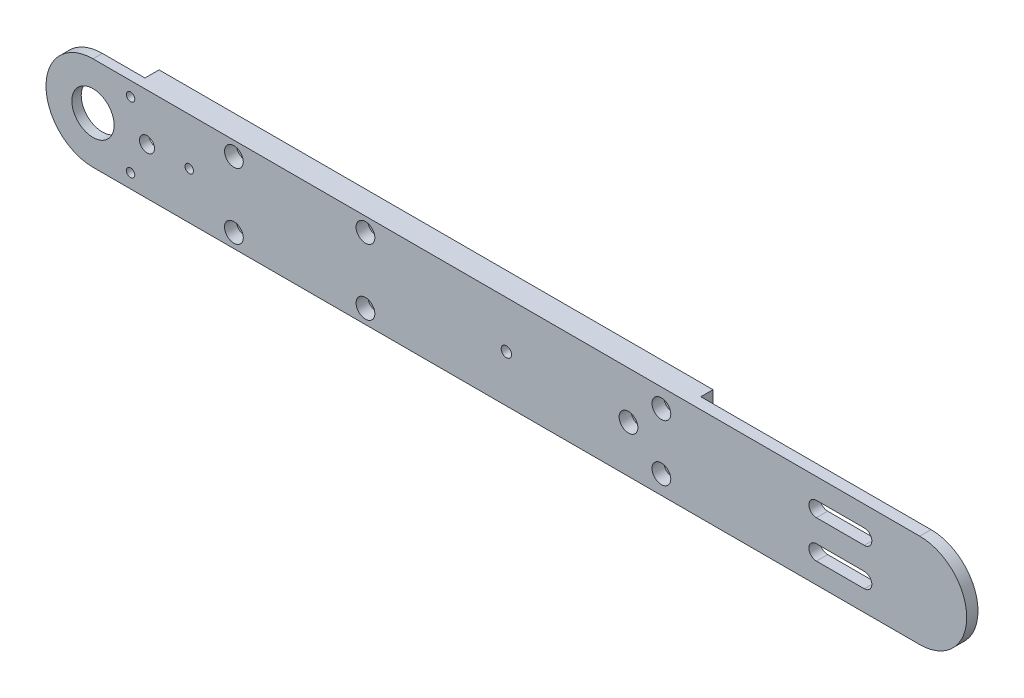
SolidWorks part; units mm, degrees
ref_plane "前视基准面" through (0, 0, 0) normal (0, 0, 1) x (1, 0, 0)
ref_plane "上视基准面" through (0, 0, 0) normal (0, 1, 0) x (1, 0, 0)
ref_plane "右视基准面" through (0, 0, 0) normal (1, 0, 0) x (0, 0, -1)
other "Configuration Table"
sketch "草图1" plane through (0, 0, 0) normal (0, 0, 1) x (1, 0, 0)
  line L0 (0, 0) -> (176, 0) construction
  line L5 (0, 10) -> (176, 10)
  line L6 (0, 10) -> (0, -10)
  line L7 (0, -10) -> (176, -10)
  line L8 (176, 10) -> (176, -10)
  circle A2 centre (0, 0) radius 10
  circle A5 centre (88, 0) radius 2.55
  circle A8 centre (88, 0) radius 1.1
  circle A9 centre (0, 0) radius 2.55
  circle A10 centre (0, 0) radius 1.1
  circle A11 centre (176, 0) radius 10
  dimension "D1" = 20
  dimension "D2" = 176
  dimension "D4" = 2.2
  dimension "D5" = 5.1
  dimension "D3" = 176
extrude "凸台-拉伸1" add sketch "草图1" along normal blind 5 contours A2 | L7 L8 L5 L6 | A11
extrude "切除-拉伸2" cut sketch "草图1<3>" along normal through all contours A10 | A8
sketch "草图1<3>" plane through (0, 0, 0) normal (0, 0, 1) x (1, 0, 0) same geometry as "草图1"
extrude "切除-拉伸3" cut sketch "草图1<4>" along normal blind 2.6 contours A5 | A9
sketch "草图1<4>" plane through (0, 0, 0) normal (0, 0, 1) x (1, 0, 0) same geometry as "草图1"
sketch "草图2" plane through (0, 0, 0) normal (0, 0, -1) x (-1, 0, 0)
  line L0 (0, -10) -> (-176, -10) construction
  line L1 (0, 10) -> (-176, 10) construction
  line L2 (-121, 6) -> (-121, -6) construction
  circle A0 centre (-121, -6) radius 1.25
  circle A1 centre (-121, 6) radius 1.25
  circle A2 centre (-121, -6) radius 2
  circle A3 centre (-121, 6) radius 2
  circle A4 centre (-88, 0) radius 1.1 construction
  circle A5 centre (-114, 0) radius 2
  circle A6 centre (-114, 0) radius 1.25
  circle A7 centre (-58, 7) radius 1.25
  circle A9 centre (-58, 7) radius 2
  circle A10 centre (-30, 7) radius 2
  circle A11 centre (-30, 7) radius 1.25
  circle A12 centre (-58, -7) radius 2
  circle A13 centre (-58, -7) radius 1.25
  circle A14 centre (-30, -7) radius 1.25
  circle A15 centre (-30, -7) radius 2
  point P16 (-121, 0)
  dimension "D1" = 4
  dimension "D2" = 2.5
  dimension "D3" = 33
  dimension "D4" = 4
  dimension "D5" = 4
  dimension "D6" = 7
  dimension "D7" = 30
  dimension "D8" = 30
  dimension "D9" = 3
  dimension "D10" = 3
extrude "切除-拉伸4" cut sketch "草图2" against normal through all contours A1 | A0 | A6 | A13 | A14 | A11 | A7
extrude "切除-拉伸5" cut sketch "草图2<3>" along normal offset from surface (2.5 mm away) 2.5 from surface contours A3 | A2 | A5 | A9 | A10 | A15 | A12 up to face at (56.75, 7, 0) starting at face at (56.75, 7, 5)
sketch "草图2<3>" plane through (0, 0, 0) normal (0, 0, -1) x (-1, 0, 0) same geometry as "草图2"
sketch "草图3" plane through (0, 10, 0) normal (0, 1, 0) x (1, 0, 0)
  line L0 (0, 0) -> (176, 0) construction
  line L1 (127, 0) -> (186, 0)
  line L2 (127, 0) -> (127, -2.6)
  line L3 (127, -2.6) -> (186, -2.6)
  line L4 (186, 0) -> (186, -2.6)
  dimension "D1" = 59
  dimension "D2" = 2.6
extrude "切除-拉伸6" cut sketch "草图3" against normal through all
sketch "草图4" plane through (0, 0, 5) normal (0, 0, 1) x (1, 0, 0)
  line L0 (164.2, -2.4) -> (154, -2.4)
  line L5 (164.2, -2.4) -> (164.2, -5.6)
  line L6 (164.2, -5.6) -> (154, -5.6)
  line L7 (154, -2.4) -> (154, -5.6)
  line L8 (164.2, 5.6) -> (154, 5.6)
  line L9 (164.2, 5.6) -> (164.2, 2.4)
  line L10 (164.2, 2.4) -> (154, 2.4)
  line L11 (154, 5.6) -> (154, 2.4)
  line L12 (154, 4) -> (154, -4)
  line L13 (186, 0) -> (154, 0)
  circle A3 centre (164.2, -4) radius 1.6
  circle A4 centre (154, -4) radius 1.6
  circle A5 centre (164.2, 4) radius 1.6
  circle A6 centre (154, 4) radius 1.6
  arc A7 (176, -10) -> (176, 10) centre (176, 0) ccw construction
  dimension "D1" = 10.2
  dimension "D3" = 3.2
  dimension "D4" = 3.2
  dimension "D2" = 8
  dimension "D5" = 32
extrude "切除-拉伸7" cut sketch "草图4" against normal through all contours A6 | L10 L11 L8 L9 | A5 | L6 L7 L0 L5 | A4 | A3
mirror "镜向1" about plane through (0, 0, 0) normal (0, 0, 1) of bodies 153
sketch "草图5" plane through (0, 0, 0) normal (0, 0, 1) x (1, 0, 0)
  line L1 (-19.6603, 11.6004) -> (191.1829, 11.6004)
  line L2 (-19.6603, 11.6004) -> (-19.6603, -13.6356)
  line L3 (-19.6603, -13.6356) -> (191.1829, -13.6356)
  line L4 (191.1829, 11.6004) -> (191.1829, -13.6356)
extrude "切除-拉伸8" cut sketch "草图5" along normal through all
sketch "草图6" plane through (0, 0, 0) normal (0, 0, 1) x (1, 0, 0)
  circle A0 centre (0, 0) radius 13.5
  dimension "D1" = 27
extrude "切除-拉伸9" cut sketch "草图6" against normal blind 3
sketch "草图7" plane through (0, 0, -5) normal (0, 0, -1) x (-1, 0, 0)
  circle A0 centre (0, 0) radius 4.5
  dimension "D1" = 9
extrude "切除-拉伸10" cut sketch "草图7" against normal through all
sketch "草图8" plane through (0, 0, -5) normal (0, 0, -1) x (-1, 0, 0)
  line L0 (0, 10) -> (-176, 10) construction
  line L1 (0, -10) -> (-176, -10) construction
  circle A0 centre (-11.5, 0) radius 1.6
  circle A1 centre (-8, 7) radius 0.9
  circle A2 centre (-8, -7) radius 0.9
  circle A3 centre (-20.5, 0) radius 0.9
  dimension "D2" = 3.2
  dimension "D3" = 1.8
  dimension "D1" = 11.5
  dimension "D4" = 3
  dimension "D5" = 3
  dimension "D6" = 8
  dimension "D7" = 12.5
extrude "切除-拉伸11" cut sketch "草图8" against normal through all
ref_plane "基准面1" through (0, 0, -15) normal (0, 0, -1) x (-1, 0, 0)
mirror "镜向2" about plane through (0, 0, -15) normal (0, 0, -1) of bodies 158
sketch "草图9" plane through (0, 0, -15) normal (0, 0, -1) x (-1, 0, 0)
  line L1 (-254.3342, 62.0115) -> (49.4551, 62.0115)
  line L2 (-254.3342, 62.0115) -> (-254.3342, -47.2362)
  line L3 (-254.3342, -47.2362) -> (49.4551, -47.2362)
  line L4 (49.4551, 62.0115) -> (49.4551, -47.2362)
  point P4 (49.4551, -47.2362)
extrude "切除-拉伸12" cut sketch "草图9" against normal through all
